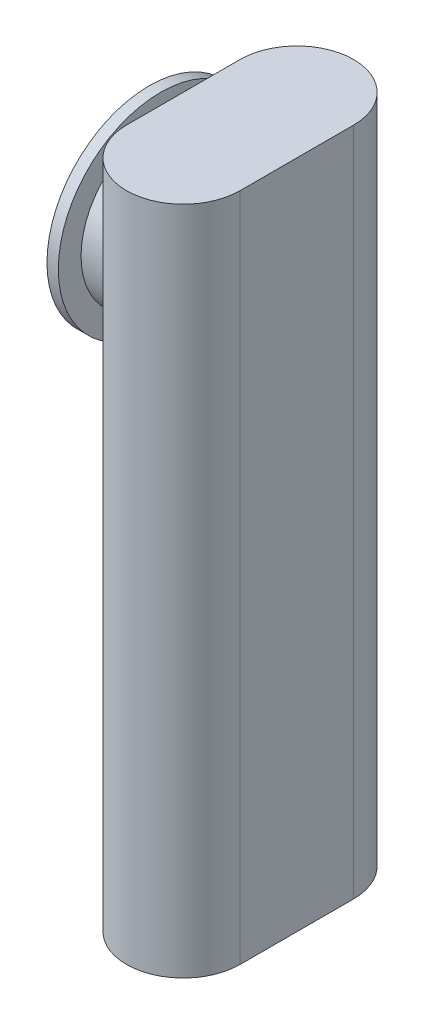
SolidWorks part; units mm, degrees
ref_plane "Plan de face" through (0, 0, 0) normal (0, 0, 1) x (1, 0, 0)
ref_plane "Plan de dessus" through (0, 0, 0) normal (0, 1, 0) x (1, 0, 0)
ref_plane "Plan de droite" through (0, 0, 0) normal (1, 0, 0) x (0, 0, -1)
sketch "Esquisse1" plane through (0, 0, 0) normal (0, 1, 0) x (1, 0, 0)
  line L1 (0, -5) -> (-19.5, -5)
  line L2 (0, -5) -> (19.5, -5)
  line L3 (0, 5) -> (19.5, 5)
  line L6 (-19.5, -5) -> (-19.5, 5)
  line L7 (-14.5, 0) -> (-19.5, 0)
  line L8 (-19.5, 5) -> (-14.5, 5)
  line L9 (-14.5, 5) -> (-14.5, -5)
  line L10 (-14.5, 5) -> (0, 5)
  line L11 (19.5, 0) -> (14.5, 0)
  line L14 (14.5, 5) -> (14.5, -5)
  line L16 (-17, -5) -> (-17, 5)
  line L17 (17, -5) -> (17, 5)
  line L18 (19.5, -5) -> (19.5, 5)
  line L19 (19.5, -2.5) -> (14.5, -2.5)
  line L21 (-15, 2.5) -> (-15, -2.5)
  line L22 (-19, -2.5) -> (-19, 2.5)
  line L23 (-14.5, -2.5) -> (-19.5, -2.5)
  line L24 (14.5, 0) -> (-14.5, 0)
  line L25 (-16, 1.5) -> (-16, -1.5)
  line L26 (-19.5, 2.5) -> (-14.5, 2.5)
  line L27 (14.5, 2.5) -> (19.5, 2.5)
  line L28 (-16, -1.5) -> (-18, -1.5)
  line L29 (-18, -1.5) -> (-18, 1.5)
  line L30 (-18, 1.5) -> (-16, 1.5)
  circle A0 centre (0, 0) radius 3.5
  circle A10 centre (0, 0) radius 5
  arc A23 (19.5, -2.5) -> (17, -5) centre (17, -2.5) cw
  arc A24 (17, -5) -> (14.5, -2.5) centre (17, -2.5) cw
  arc A25 (17, 5) -> (14.5, 2.5) centre (17, 2.5) ccw
  arc A26 (17, 5) -> (19.5, 2.5) centre (17, 2.5) cw
  arc A27 (-17, 5) -> (-19.5, 2.5) centre (-17, 2.5) ccw
  arc A28 (-14.5, 2.5) -> (-17, 5) centre (-17, 2.5) ccw
  arc A29 (-14.5, -2.5) -> (-17, -5) centre (-17, -2.5) cw
  arc A30 (-17, -5) -> (-19.5, -2.5) centre (-17, -2.5) cw
  arc A31 (-15, 2.5) -> (-19, 2.5) centre (-17, 2.5) ccw
  arc A32 (-15, -2.5) -> (-19, -2.5) centre (-17, -2.5) cw
  point P44 (-17, 4.5)
  point P45 (-17, -4.5)
  dimension "D1" = 7
  dimension "D2" = 10
  dimension "D3" = 14.5
  dimension "D6" = 2.5
  dimension "D8" = 2.5
  dimension "D9" = 2.5
  dimension "D11" = 2.5
  dimension "D10" = 2.5
  dimension "D12" = 2.5
  dimension "D13" = 0.5
  dimension "D4" = 2.5
  dimension "D5" = 14.5
  dimension "D7" = 2.5
  dimension "D15" = 0.5
  dimension "D16" = 0.5
  dimension "D17" = 1
  dimension "D18" = 1
  dimension "D20" = 1
extrude "Boss.-Extru.6" add sketch "Esquisse1" along normal blind 28 separate body contours A31 L26 A28 L16 | L26 A31 L16 | A31 L16 A27 L26 | L16 A31 L26 | L26 L16 L7 L21 | L26 L21 L7 L9 | L23 L9 L7 L21 | L23 L21 L7 | L23 L7 L22 | L26 L22 L7 L16 | L26 L6 L7 L22 | L23 L22 L7 L6 | A32 L23 A30 | A32 L16 L23 | A32 L23 L16 | L23 A32 A29 | L30 L16 L7 L25 | L30 L29 L7 L16 | L29 L28 L7 | L28 L25 L7 region at (-18.4383, 0, 3.9383) region at (-15.5617, 0, 3.9383) region at (-14.75, 0, 1.25) region at (-14.75, 0, -1.25) region at (-17.8488, 0, 3.3488) region at (-16.1512, 0, 3.3488) region at (-19.25, 0, 1.25) region at (-15.7857, 0, 1.4643) region at (-15.7857, 0, -1.4643) region at (-15.5617, 0, -3.9383) region at (-18.2143, 0, 1.4643) region at (-19.25, 0, -1.25) region at (-18.4383, 0, -3.9383) region at (-16.5, 0, 0.75) region at (-16.5, 0, -0.75) region at (-16.1512, 0, -3.3488) region at (-17.5, 0, 0.75) region at (-18.2143, 0, -1.4643) region at (-17.8488, 0, -3.3488) region at (-17.5, 0, -0.75)
extrude "Boss.-Extru.7" add sketch "Esquisse1<12>" against normal blind 1.5 contours L26 L21 L7 L9 | A31 L26 A28 L16 | A31 L16 A27 L26 | L26 L6 L7 L22 | L23 L22 L7 L6 | A32 L23 A30 | L23 A32 A29 | L23 L9 L7 L21 region at (-18.4383, 0, 3.9383) region at (-15.5617, 0, 3.9383) region at (-14.75, 0, 1.25) region at (-14.75, 0, -1.25) region at (-19.25, 0, 1.25) region at (-15.5617, 0, -3.9383) region at (-19.25, 0, -1.25) region at (-18.4383, 0, -3.9383)
sketch "Esquisse1<12>" plane through (0, 0, 0) normal (0, 1, 0) x (1, 0, 0) same geometry as "Esquisse1"
sketch "Esquisse2" plane through (-19.5, 0, 0) normal (-1, 0, 0) x (0, 0, 1)
  line L0 (0, 28) -> (0, 23)
  line L1 (2.5, 28) -> (-2.5, 28) construction
  circle A0 centre (0, 23) radius 3.5
  circle A1 centre (0, 23) radius 2.5
  circle A2 centre (0, 23) radius 4.5
  line M2 (-2.5, 28) -> (-2.5, -1.5)
  line M4 (2.5, -1.5) -> (2.5, 28)
  dimension "D2" = 7
  dimension "D3" = 5
  dimension "D4" = 9
  dimension "D1" = 5
extrude "Boss.-Extru.9" add sketch "Esquisse2" along normal blind 1 and the other way blind 0.5 separate body contours A1 A0 M2 M4 | A1 L0 A0 M2 | A1 A0 L0 M4 | A0 M4 | A0 M2 region at (-19.5, 25.4784, 1.3827) region at (-19.5, 25.4784, -1.3827) region at (-19.5, 23, 2.9053) region at (-19.5, 23, -2.9053) region at (-19.5, 21.7753, 2.439)
extrude "Enlèv. mat.-Extru.1" cut sketch "Esquisse2<5>" against normal blind 1.75 contours A1 region at (-19.5, 24.7178, 1.7178)
sketch "Esquisse2<5>" plane through (-19.5, 0, 0) normal (-1, 0, 0) x (0, 0, 1) same geometry as "Esquisse2"
extrude "Enlèv. mat.-Extru.2" cut sketch "Esquisse1<17>" along normal blind 25.5 contours L29 L28 L16 L7 | L28 L25 L7 L16 | L30 L16 L7 L25 | L30 L29 L7 L16 | L26 A31 L16 | L16 A31 L26 | L29 L30 L16 L26 L22 L7 | L16 L30 L25 L7 L21 L26 | L25 L28 L16 L23 L21 L7 | L28 L29 L7 L22 L23 L16 | A32 L16 L23 | A32 L23 L16 region at (-17.8488, 0, 3.3488) region at (-16.1512, 0, 3.3488) region at (-15.7857, 0, 1.4643) region at (-15.7857, 0, -1.4643) region at (-18.2143, 0, 1.4643) region at (-16.5, 0, 0.75) region at (-16.5, 0, -0.75) region at (-16.1512, 0, -3.3488) region at (-17.5, 0, 0.75) region at (-18.2143, 0, -1.4643) region at (-17.8488, 0, -3.3488) region at (-17.5, 0, -0.75)
sketch "Esquisse1<17>" plane through (0, 0, 0) normal (0, 1, 0) x (1, 0, 0) same geometry as "Esquisse1"
sketch "Esquisse3" plane through (-20.5, 0, 0) normal (-1, 0, 0) x (0, 0, 1)
  line L0 (0, 19.5) -> (0, 26.5)
  circle A0 centre (0, 23) radius 3.5 construction
  circle A1 centre (0, 23) radius 4.5
  circle M1 centre (0, 23) radius 2.5
  circle M2 centre (0, 23) radius 3.5
  dimension "D1" = 9
extrude "Boss.-Extru.10" add sketch "Esquisse3" along normal blind 0.5 contours A1 M2 | L0 M2 M1 | L0 M2 M1 region at (-20.5, 23, -3.4217) region at (-20.5, 20, 0.0783) region at (-20.5, 23, -4.3727)
